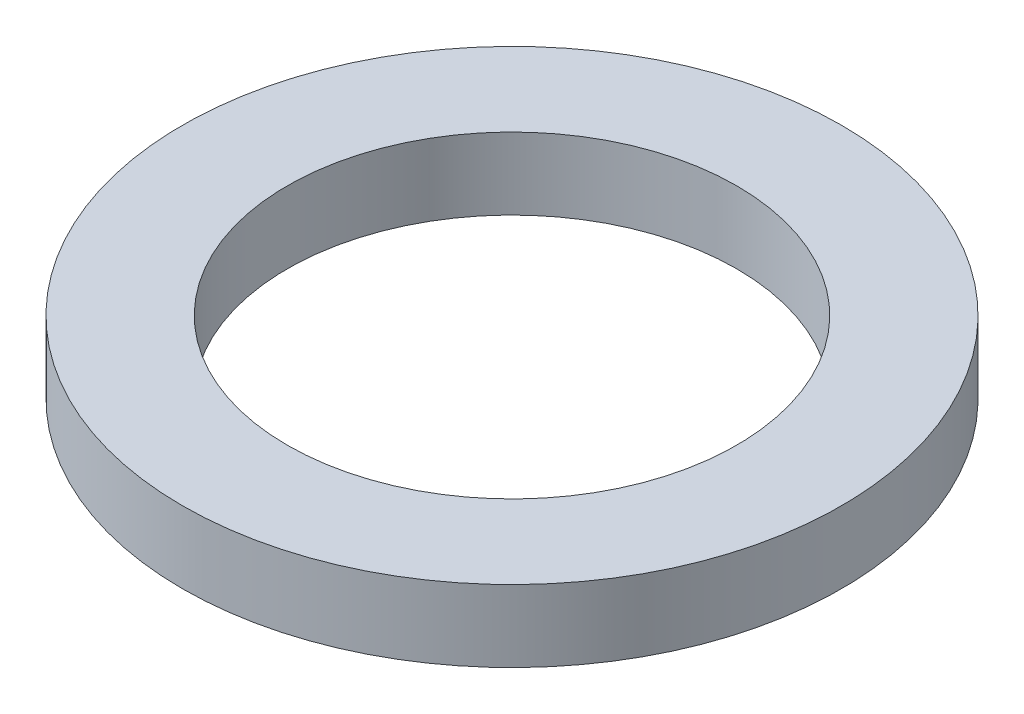
SolidWorks part; units mm, degrees
ref_plane "Front Plane" through (0, 0, 0) normal (0, 0, 1) x (1, 0, 0)
ref_plane "Top Plane" through (0, 0, 0) normal (0, 1, 0) x (1, 0, 0)
ref_plane "Right Plane" through (0, 0, 0) normal (1, 0, 0) x (0, 0, -1)
sketch "Sketch1" plane through (0, 0, 0) normal (0, 1, 0) x (1, 0, 0)
  circle A0 centre (0, 0) radius 55
  dimension "FLANGE_OD" = 110
extrude "Boss-Extrude1" add sketch "Sketch1" along normal blind 12
sketch "Sketch2" plane through (0, 0, 0) normal (0, 1, 0) x (1, 0, 0)
  circle A0 centre (0, 0) radius 37.5
  dimension "BORE_D" = 75
extrude "Cut-Extrude1" cut sketch "Sketch2" along normal through all
sketch "Sketch3" plane through (0, 12, 0) normal (0, 1, 0) x (1, 0, 0)
  circle A0 centre (0, 0) radius 21.6295 construction
  circle A1 centre (-21.6295, 0) radius 2.2445
  dimension "BOLT_D" = 4.4891
  dimension "BOLT_PCD" = 43.2589
extrude "Cut-Extrude2" cut sketch "Sketch3" against normal blind 11.7369 rebuild error yes
pattern_circular "CirPattern1" count 8 over 360 rebuild error yes
